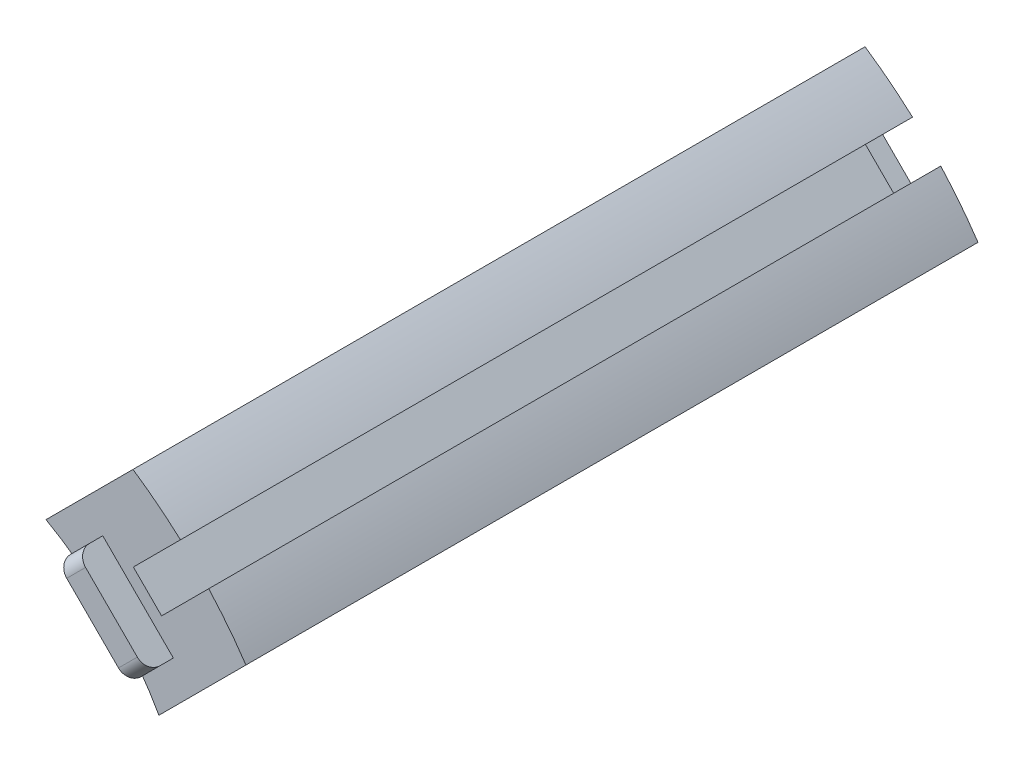
SolidWorks part; units mm, degrees
ref_plane "Ön Düzlem" through (0, 0, 0) normal (0, 0, 1) x (1, 0, 0)
ref_plane "Üst Düzlem" through (0, 0, 0) normal (0, 1, 0) x (1, 0, 0)
ref_plane "Sağ Düzlem" through (0, 0, 0) normal (1, 0, 0) x (0, 0, -1)
sketch "Sketch1" plane through (0, 0, 0) normal (0, 0, 1) x (1, 0, 0)
  line L0 (-0.0847, -0.0064) -> (44.1095, 44.1877) construction
  line L1 (34.802, 51.8508) -> (21.7306, 38.7794)
  line L2 (51.7726, 34.8802) -> (38.7012, 21.8089)
  line L3 (41.9373, 46.2581) -> (34.8565, 39.1773)
  line L4 (34.8565, 39.1773) -> (39.0991, 34.9347)
  line L5 (39.0991, 34.9347) -> (46.1799, 42.0155)
  line L6 (-0.0847, -0.0064) -> (-0.0847, 62.4936) construction
  line L7 (30.2603, 40.9451) -> (27.4319, 38.1167)
  line L8 (27.4319, 38.1167) -> (38.0385, 27.5101)
  line L9 (38.0385, 27.5101) -> (40.8669, 30.3385)
  line L10 (40.8669, 30.3385) -> (30.2603, 40.9451)
  line L11 (34.8565, 39.1773) -> (28.4925, 45.5413) construction
  circle A0 centre (-0.0847, -0.0064) radius 62.5
  circle A1 centre (-0.0847, -0.0064) radius 44.5
  point P17 (35.5636, 35.6418)
  point P19 (38.3969, 42.7177)
  point P20 (36.9778, 37.056)
  dimension "D1" = 125
  dimension "D2" = 89
  dimension "D3" = 45
  dimension "D4" = 4
  dimension "D5" = 15
  dimension "D6" = 4
  dimension "D7" = 9
  dimension "D8" = 9
  dimension "D9" = 6
extrude "Boss-Extrude1" add sketch "Sketch1" along normal blind 110 contours A1 L2 A0 L5 L4 L3 L1 L10 L9 L8 L7 | L9 L10 L7 L8 region at (38.2091, 48.8496, 0) region at (34.1494, 34.2276, 0)
sketch "Sketch2" plane through (2.0822, -2.0822, 0) normal (-0.7071, 0.7071, 0) x (0, 0, 1)
  line L0 (85, 57.3567) -> (115, 57.3567) construction
  line L1 (115, 57.3567) -> (120, 57.3567) construction
  line L2 (25, 57.3567) -> (-5, 57.3567) construction
  line L3 (25, 57.3567) -> (55, 57.3567) construction
  line L4 (55, 57.3567) -> (85, 57.3567) construction
  line L5 (-5, 57.3567) -> (-10, 57.3567) construction
  line L9 (0, 52.3498) -> (0, 62.3636) construction
  line L10 (110, 52.3498) -> (110, 62.3636) construction
  circle A0 centre (85, 57.3567) radius 3
  circle A1 centre (55, 57.3567) radius 3
  circle A2 centre (25, 57.3567) radius 3
  point P24 (110, 57.3567)
  dimension "D1" = 6
  dimension "D2" = 5
  dimension "D3" = 130
  dimension "D4" = 5
  dimension "D5" = 5
extrude "Cut-Extrude1" cut sketch "Sketch2" against normal mid plane 110
extrude "Boss-Extrude2" add sketch "Sketch1<5>" along normal blind 114 and the other way blind 4 contours L9 L10 L7 L8 region at (34.1494, 34.2276, 0)
sketch "Sketch1<5>" plane through (0, 0, 0) normal (0, 0, 1) x (1, 0, 0) same geometry as "Sketch1"
fillet "Fillet1" radius 2 4 edges at (28.8461, 39.5309, 114) (39.4527, 28.9243, 114) (28.8461, 39.5309, -4) (39.4527, 28.9243, -4)
